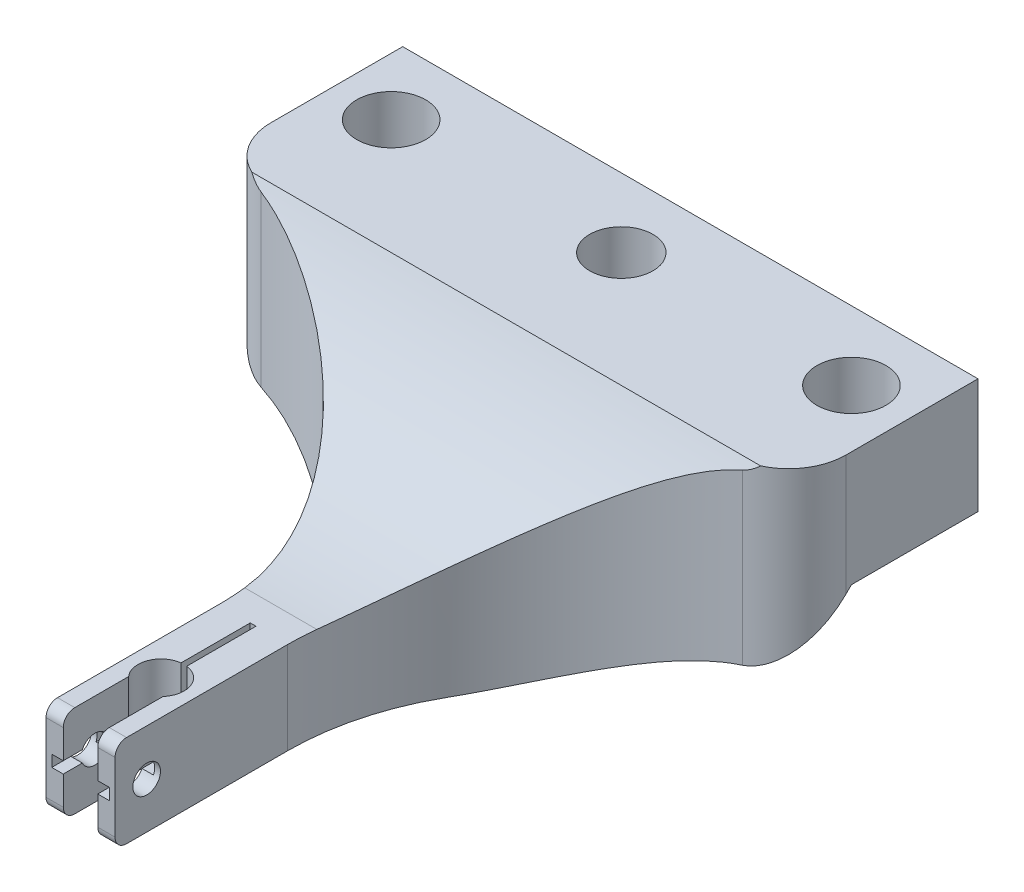
SolidWorks part; units mm, degrees
ref_plane "Front Plane" through (0, 0, 0) normal (0, 0, 1) x (1, 0, 0)
ref_plane "Top Plane" through (0, 0, 0) normal (0, 1, 0) x (1, 0, 0)
ref_plane "Right Plane" through (0, 0, 0) normal (1, 0, 0) x (0, 0, -1)
sketch "Sketch1" plane through (0, 0, 0) normal (0, 1, 0) x (1, 0, 0)
  line L0 (0, 0) -> (0, 40) construction
  line L1 (-20, 40) -> (20, 40) construction
  line L3 (-25, 46) -> (-25, 30)
  line L6 (-25, 46) -> (25, 46)
  line L7 (25, 46) -> (25, 30)
  line L11 (3, 30) -> (25, 30)
  line L12 (-3, 30) -> (-25, 30)
  line L13 (3, 30) -> (3, -7)
  line L14 (3, -7) -> (-3, -7)
  line L15 (-3, -7) -> (-3, 30)
  line L18 (0, 0) -> (0, -7) construction
  circle A1 centre (-20, 40) radius 3
  circle A2 centre (20, 40) radius 3
  circle A3 centre (0, 40) radius 2.75
  point P12 (0, 46)
  point P22 (0, -7)
  dimension "D3" = 10
  dimension "D4" = 16
  dimension "D5" = 6
  dimension "D6" = 6
  dimension "D7" = 5.5
  dimension "D2" = 6
  dimension "D9" = 7
  dimension "D10" = 40
  dimension "D11" = 50
  dimension "D16" = 40
extrude "Boss-Extrude1" add sketch "Sketch1" along normal blind 20 contours L11 L7 L6 L3 L12 A3 A2 A1 region at (0, 0, -31.5822)
fillet "Fillet8" radius 22 2 edges at (3, 10, -30) (-3, 10, -30)
sketch "Sketch2" plane through (0, 0, 0) normal (0, 1, 0) x (1, 0, 0)
  circle A0 centre (0, 0) radius 2
  dimension "D1" = 4
extrude "Cut-Extrude1" cut sketch "Sketch2" along normal up to surface (20 mm away) up to face at (0, 20, -37.25)
sketch "Sketch4" plane through (0, 0, 0) normal (0, -1, 0) x (-1, 0, 0)
  circle A0 centre (0, 0) radius 2.5
  dimension "D1" = 5
extrude "Cut-Extrude2" cut sketch "Sketch4" against normal blind 1 from offset 3.5 offset against normal yes
sketch "Sketch5" plane through (0, 20, 0) normal (0, 1, 0) x (1, 0, 0)
  line L0 (0, 8) -> (0, -7) construction
  line L1 (0, 8) -> (-0.25, 8)
  line L2 (-0.25, 8) -> (-0.25, 0)
  line L3 (-0.25, 0) -> (-1.5, 0)
  line L4 (-1.5, 0) -> (-1.5, -7)
  line L5 (-1.5, -7) -> (1.5, -7)
  line L6 (1.5, -7) -> (1.5, 0)
  line L7 (1.5, 0) -> (0.25, 0)
  line L8 (0.25, 0) -> (0.25, 8)
  line L9 (0.25, 8) -> (0, 8)
  line L10 (3, -7) -> (-3, -7) construction
  point P2 (0, -7)
  dimension "D1" = 8
  dimension "D2" = 0.25
  dimension "D3" = 1.5
extrude "Cut-Extrude3" cut sketch "Sketch5" against normal up to surface (20 mm away) up to face at (0, 0, 2)
sketch "Sketch6" plane through (0, 0, 0) normal (0, 0, 1) x (1, 0, 0)
  line L1 (-2.5, 3.5) -> (2.5, 3.5)
  line L2 (-2.5, 3.5) -> (-2.5, 4.5)
  line L3 (-2.5, 4.5) -> (2.5, 4.5)
  line L4 (2.5, 3.5) -> (2.5, 4.5)
extrude "Cut-Extrude4" cut sketch "Sketch6" along normal blind 10
sketch "Sketch8" plane through (-3, 0, 0) normal (-1, 0, 0) x (0, 0, 1)
  line L1 (7, 0) -> (-8, 0) construction
  line L2 (7, 20) -> (7, 0) construction
  circle A0 centre (4.25, 4) radius 1.2
  dimension "D1" = 2.4
  dimension "D2" = 2.75
  dimension "D3" = 4
extrude "Cut-Extrude5" cut sketch "Sketch8" against normal blind 10
sketch "Sketch9" plane through (-25, 0, 0) normal (-1, 0, 0) x (0, 0, 1)
  line L0 (-30, 8) -> (7, 8)
  line L3 (7, 8) -> (7, 20)
  line L4 (7, 20) -> (-30, 20)
  line L5 (-30, 20) -> (-30, 8)
  dimension "D1" = 12
extrude "Cut-Extrude6" cut sketch "Sketch9" against normal up to surface (50 mm away) up to face at (25, 10, -38)
fillet "Fillet9" radius 22 1 edges at (0, 8, -30)
sketch "Sketch10" plane through (-25, 0, 0) normal (-1, 0, 0) x (0, 0, 1)
  line L0 (-30, 20) -> (-30, 0) construction
  line L1 (-46, 0) -> (-30, 0)
  line L2 (-46, 0) -> (-46, 10)
  line L3 (-46, 10) -> (-30, 10)
  line L4 (-30, 0) -> (-30, 10)
extrude "Cut-Extrude7" cut sketch "Sketch10" against normal up to surface (50 mm away) up to face at (25, 10, -38)
fillet "Fillet10" radius 5 1 edges at (0, 10, -30) profile chamfer
fillet "Fillet11" radius 15 1 edges at (0, 0, -30)
fillet "Fillet12" radius 5 2 edges at (25, 12.5, -30) (-25, 12.5, -30)
fillet "Fillet7" radius 1 4 edges at (-2.25, 0, 7) (2.25, 0, 7) (-2.25, 8, 7) (2.25, 8, 7)
sketch "Sketch12" plane through (0, -12.5, -12.5) normal (0, -0.7071, -0.7071) x (1, 0, 0)
  line L0 (0, -31.8198) -> (0, -24.7487) construction
  line L1 (25, -31.8198) -> (-25, -31.8198) construction
  line L2 (-22.11, -24.7487) -> (22.11, -24.7487) construction
  line L3 (-12.3319, -30.0228) -> (12.3319, -30.0228) construction
  text T0 "Jadhav Lab"
extrude "Boss-Extrude3" add sketch "Sketch12" along normal blind 0.5
equation "\"3.5.00mm\"=2"
